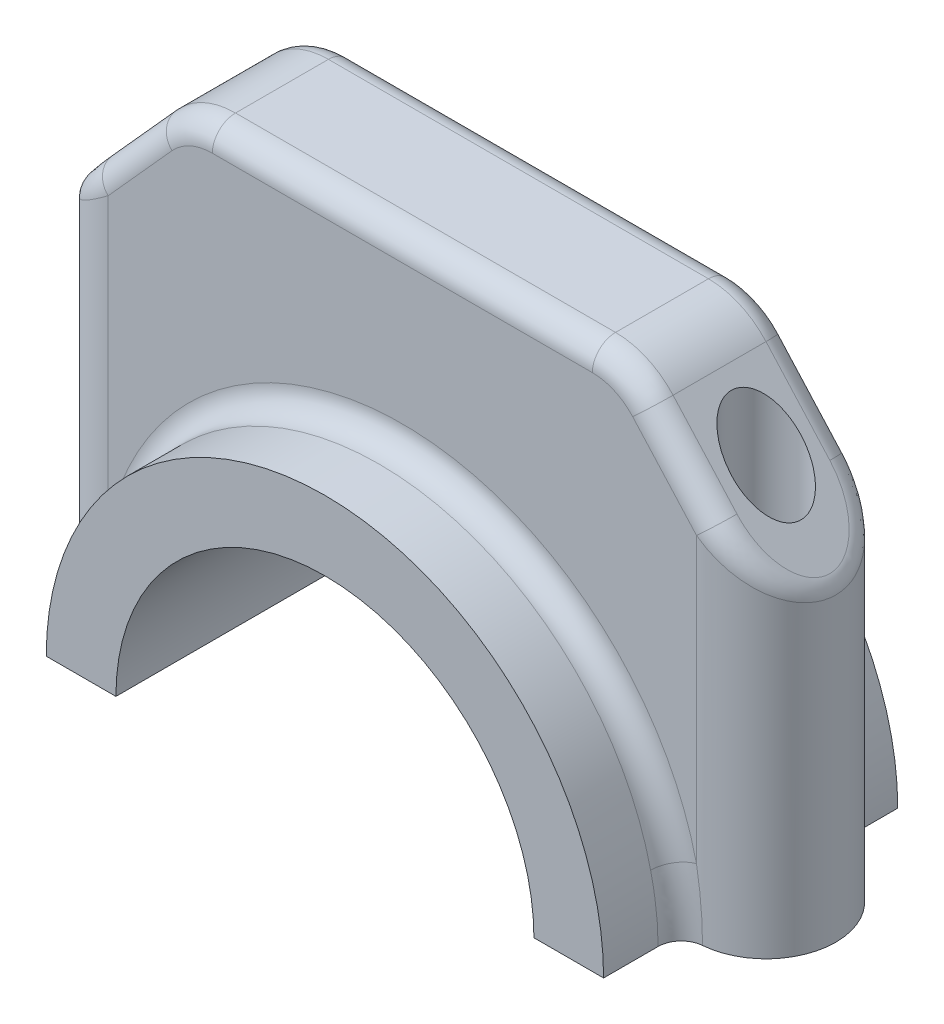
SolidWorks part; units mm, degrees
ref_plane "Front Plane" through (0, 0, 0) normal (0, 0, 1) x (1, 0, 0)
ref_plane "Top Plane" through (0, 0, 0) normal (0, 1, 0) x (1, 0, 0)
ref_plane "Right Plane" through (0, 0, 0) normal (1, 0, 0) x (0, 0, -1)
sketch "Sketch1" plane through (0, 0, 0) normal (0, 0, 1) x (1, 0, 0)
  line L0 (-36, 0) -> (-27, 0)
  line L1 (27, 0) -> (36, 0)
  arc A0 (36, 0) -> (-36, 0) centre (0, 0) ccw
  arc A1 (27, 0) -> (-27, 0) centre (0, 0) ccw
  dimension "D1" = 72
  dimension "D2" = 54
extrude "Boss-Extrude1" add sketch "Sketch1" along normal mid plane 38
ref_plane "Plane1" through (0, 60, 0) normal (0, -1, 0) x (-1, 0, 0)
sketch "Sketch4" plane through (0, 60, 0) normal (0, -1, 0) x (-1, 0, 0)
  line L0 (-44.9933, 0) -> (49.0929, 0) construction
  line L1 (38, 0) -> (-38, 0) construction
  line L2 (38, -9) -> (-38, -9)
  line L3 (38, 9) -> (-38, 9)
  arc A0 (38, -9) -> (38, 9) centre (38, 0) ccw
  arc A1 (-38, 9) -> (-38, -9) centre (-38, 0) ccw
  point P5 (0, 0)
  dimension "D2" = 9
  dimension "D1" = 76
extrude "Boss-Extrude2" add sketch "Sketch4" along normal up to surface (60 mm away) up to face at (-31.5, 0, 0)
sketch "Sketch5" plane through (0, 0, 9) normal (0, 0, 1) x (1, 0, 0)
  line L1 (-27, 0) -> (27, 0)
  line L2 (-27, 0) -> (27, 0)
  arc A1 (27, 0) -> (-27, 0) centre (0, 0) ccw
  arc A2 (27, 0) -> (-27, 0) centre (0, 0) ccw
  dimension "D1" = 0
extrude "Cut-Extrude1" cut sketch "Sketch5" against normal through all
sketch "Sketch6" plane through (0, 60, 0) normal (0, 1, 0) x (1, 0, 0)
  circle A0 centre (-38, 0) radius 4.5
  circle A1 centre (38, 0) radius 4.5
extrude "Cut-Extrude2" cut sketch "Sketch6" against normal blind 86
sketch "Sketch8" plane through (0, 0, 0) normal (0, 0, 1) x (1, 0, 0)
  line L0 (-47, 60) -> (-47, 40)
  line L1 (-47, 60) -> (-29, 60)
  line L2 (38, 60) -> (-38, 60) construction
  line L3 (-29, 60) -> (-47, 40)
  line L4 (0, 0) -> (0, 71.6388) construction
  line L5 (29, 60) -> (47, 40)
  line L6 (47, 60) -> (29, 60)
  line L7 (47, 60) -> (47, 40)
extrude "Cut-Extrude3" cut sketch "Sketch8" against normal mid plane 86
fillet "Fillet1" radius 10 2 edges at (29, 60, 0) (-29, 60, 0)
fillet "Fillet2" radius 3 2 edges at (0, 36, -9) (0, 36, 9)
fillet "Fillet3" radius 3 12 edges at (28.6148, 59.135, 9) (34.9897, 53.3448, 9) (47, 40, 0) (34.9897, 53.3448, -9) (28.6148, 59.135, -9) (-28.6148, 59.135, -9) (-34.9897, 53.3448, -9) (-47, 40, 0) (-34.9897, 53.3448, 9) (-28.6148, 59.135, 9) (0, 60, -9) (0, 60, 9)
